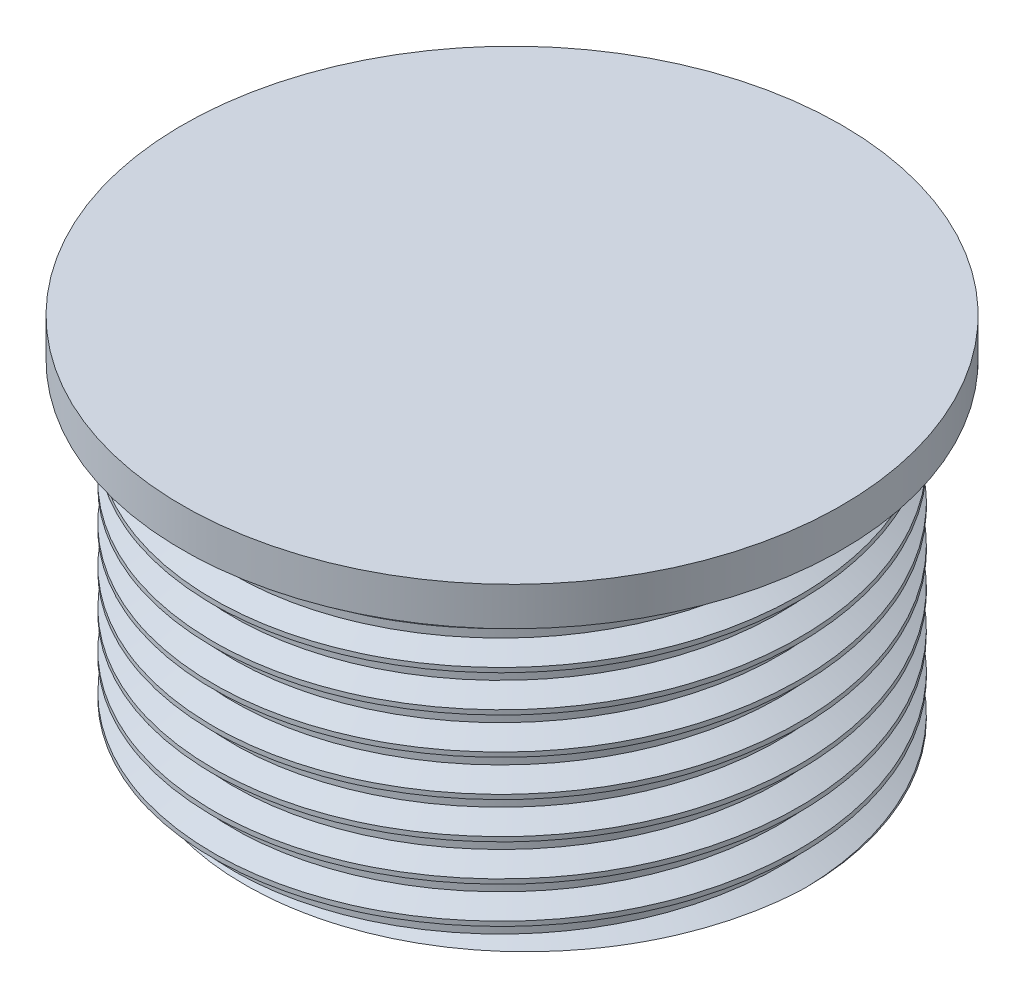
SolidWorks part; units mm, degrees
material "AISI Тип 316L нержавеющая сталь"
ref_plane "Спереди" through (0, 0, 0) normal (0, 0, 1) x (1, 0, 0)
ref_plane "Сверху" through (0, 0, 0) normal (0, 1, 0) x (1, 0, 0)
ref_plane "Справа" through (0, 0, 0) normal (1, 0, 0) x (0, 0, -1)
sketch "Эскиз1" plane through (0, 0, 0) normal (0, 0, 1) x (1, 0, 0)
  line L0 (0, 7.0462) -> (0, 9.5462)
  line L1 (0, 9.5462) -> (-9, 9.5462)
  line L2 (-9, 9.5462) -> (-9, 8.4961)
  line L3 (-9, 8.4961) -> (-7.35, 8.4961)
  line L4 (-7.35, 8.4961) -> (-7.35, 7.5415)
  line L5 (-7.35, 7.5415) -> (-8, 7.5415)
  line L6 (-8, 7.5415) -> (-8, 0)
  line L7 (-8, 0) -> (-7, 0)
  line L8 (0, 7.0462) -> (-7, 7.0462)
  line L9 (-7, 7.0462) -> (-7, 0)
  line L10 (0, 9.5462) -> (0, 0) construction
  point P10 (-7.35, 8.0188)
  dimension "D3" = 1.65
  dimension "D4" = 1
  dimension "D5" = 2.5
revolve "Повернуть1" add sketch "Эскиз1" angle 360 about L0
thread "Резьба2" pitch 1 start angle 0, offset 2, length 0, pitch 1, diameter 16
ref_plane "Плоскость2" through (8, -2, 0) normal (0, 0, 1) x (1, 0, 0)
sketch "Профиль резьбы2" plane through (8, -2, 0) normal (0, 0, 1) x (1, 0, 0)
  line L0 (0, 0) -> (0, 1) construction
  line L11 (0, 0) -> (0, 0.875)
  line L12 (0, 0.875) -> (-0.5413, 0.5625)
  line L13 (-0.5413, 0.5625) -> (-0.5413, 0.3125)
  line L15 (-0.5413, 0.3125) -> (0, 0)
  line L17 (-0.5413, 0.4375) -> (0, 0.4375) construction
  point P2 (0, 0)
  dimension "Pitch" = 1
  dimension "Profile_Angle" = 60
  dimension "Profile_Land" = 0.25
  dimension "Profile_Height" = 0.5413
